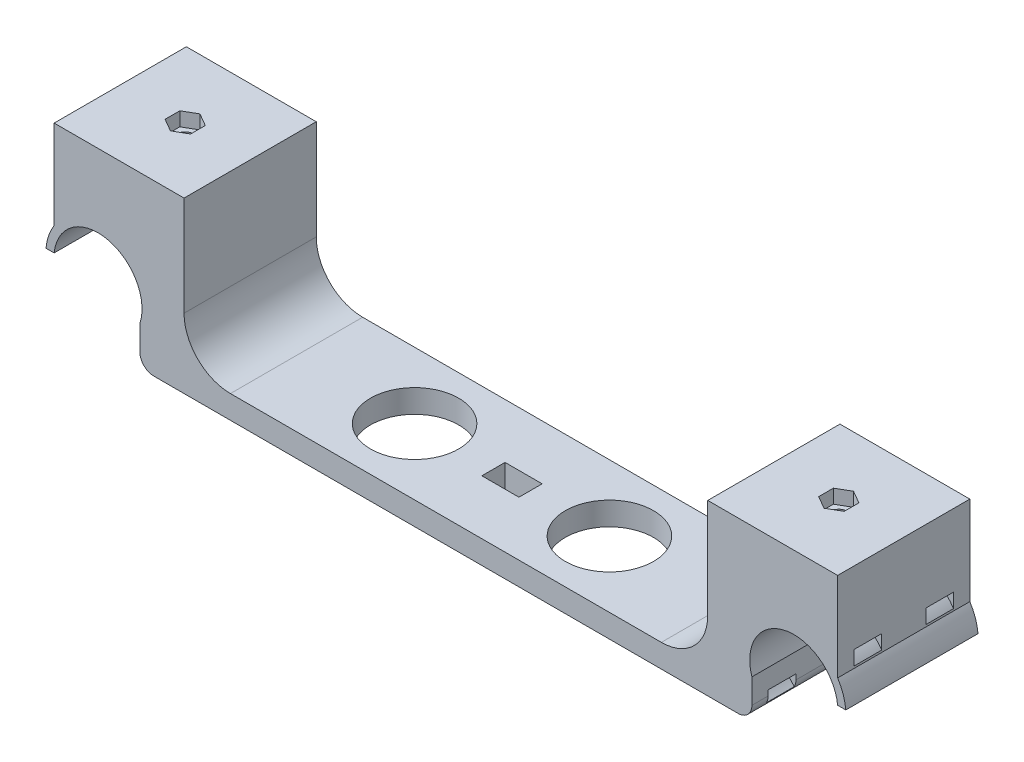
SolidWorks part; units mm, degrees
ref_plane "Front Plane" through (0, 0, 0) normal (0, 0, 1) x (1, 0, 0)
ref_plane "Top Plane" through (0, 0, 0) normal (0, 1, 0) x (1, 0, 0)
ref_plane "Right Plane" through (0, 0, 0) normal (1, 0, 0) x (0, 0, -1)
sketch "Sketch7" plane through (0, 0, 0) normal (0, 0, 1) x (1, 0, 0)
  line L0 (-35.0092, -3.4353) -> (114.9908, -3.4353)
  line L1 (-16.4565, 1.5647) -> (96.438, 1.5647)
  line L8 (126.1962, 6.8147) -> (124.438, 6.8147)
  line L9 (126.1962, 8.8147) -> (124.438, 8.8147)
  line L10 (39.9908, -3.4353) -> (39.9908, 54.826) construction
  line L11 (-46.2147, 8.8147) -> (-44.4565, 8.8147)
  line L12 (-46.2147, 6.8147) -> (-44.4565, 6.8147)
  line L19 (-44.4565, 13.9231) -> (-44.4565, 33.0647)
  line L20 (-44.4565, 33.0647) -> (-16.4565, 33.0647)
  line L21 (-16.4565, 33.0647) -> (-16.4565, 1.5647)
  line L22 (96.438, 33.0647) -> (96.438, 1.5647)
  line L23 (124.438, 13.9231) -> (124.438, 33.0647)
  line L24 (124.438, 33.0647) -> (96.438, 33.0647)
  arc A0 (124.438, 8.8147) -> (124.438, 6.8147) centre (114.9908, 7.8147) ccw
  arc A1 (-44.4565, 6.8147) -> (-44.4565, 8.8147) centre (-35.0092, 7.8147) ccw
  arc A2 (114.9908, -3.4353) -> (126.1962, 6.8147) centre (114.9908, 7.8147) ccw
  arc A3 (-44.4565, 13.9231) -> (-46.2147, 8.8147) centre (-35.0092, 7.8147) ccw
  arc A4 (-46.2147, 6.8147) -> (-35.0092, -3.4353) centre (-35.0092, 7.8147) ccw
  arc A5 (126.1962, 8.8147) -> (124.438, 13.9231) centre (114.9908, 7.8147) ccw
  dimension "D2" = 19
  dimension "D3" = 1.75
  dimension "D11" = 28
  dimension "D5" = 2
  dimension "D1" = 150
  dimension "D4" = 5
  dimension "D6" = 1
  dimension "D12" = 31.5
extrude "Boss-Extrude3" add sketch "Sketch7" along normal blind 28.5
fillet "Fillet1" radius 10 2 edges at (96.438, 1.5647, 14.25) (-16.4565, 1.5647, 14.25)
sketch "Sketch8" plane through (0, 1.5647, 0) normal (0, 1, 0) x (1, 0, 0)
  line L0 (39.9908, 0) -> (39.9908, -28.5) construction
  line L1 (86.438, 0) -> (-6.4565, 0) construction
  line L2 (86.438, -28.5) -> (-6.4565, -28.5) construction
  line L3 (86.438, -14.25) -> (-6.4565, -14.25) construction
  line L4 (35.9908, -11.75) -> (43.9908, -11.75)
  line L5 (35.9908, -11.75) -> (35.9908, -16.75)
  line L6 (35.9908, -16.75) -> (43.9908, -16.75)
  line L7 (43.9908, -11.75) -> (43.9908, -16.75)
  line L8 (86.438, -28.5) -> (86.438, 0) construction
  line L9 (-6.4565, 0) -> (-6.4565, -28.5) construction
  circle A0 centre (60.9908, -14.25) radius 9.5
  circle A1 centre (18.9908, -14.25) radius 9.5
  dimension "D5" = 19
  dimension "D7" = 21
  dimension "D1" = 5
  dimension "D2" = 8
  dimension "D3" = 4
  dimension "D4" = 2.5
  dimension "D6" = 21
extrude "Cut-Extrude4" cut sketch "Sketch8" against normal up to surface (5 mm away) up to face at (39.9908, -3.4353, 14.25)
sketch "Sketch10" plane through (0, 33.0647, 0) normal (0, 1, 0) x (1, 0, 0)
  line L0 (124.438, -14.25) -> (-44.4565, -14.25) construction
  line L1 (124.438, -28.5) -> (124.438, 0) construction
  line L2 (-44.4565, -28.5) -> (-44.4565, 0) construction
  line L10 (-16.4565, -28.5) -> (-44.4565, 0) construction
  line L11 (96.438, 0) -> (124.438, -28.5) construction
  circle A0 centre (110.438, -14.25) radius 1.75
  circle A1 centre (-30.4565, -14.25) radius 1.75
  dimension "D1" = 3.5
extrude "Cut-Extrude6" cut sketch "Sketch10" against normal blind 10
sketch "Sketch13" plane through (0, 33.0647, 0) normal (0, 1, 0) x (1, 0, 0)
  line L1 (107.688, -12.6623) -> (107.688, -15.8377)
  line L2 (107.688, -15.8377) -> (110.438, -17.4254)
  line L3 (110.438, -17.4254) -> (113.188, -15.8377)
  line L4 (113.188, -15.8377) -> (113.188, -12.6623)
  line L5 (113.188, -12.6623) -> (110.438, -11.0746)
  line L6 (110.438, -11.0746) -> (107.688, -12.6623)
  line L7 (-30.4565, -17.4254) -> (-27.7065, -15.8377)
  line L8 (-27.7065, -15.8377) -> (-27.7065, -12.6623)
  line L9 (-27.7065, -12.6623) -> (-30.4565, -11.0746)
  line L10 (-30.4565, -11.0746) -> (-33.2065, -12.6623)
  line L11 (-33.2065, -12.6623) -> (-33.2065, -15.8377)
  line L12 (-33.2065, -15.8377) -> (-30.4565, -17.4254)
  line L13 (126.1962, -28.5) -> (126.1962, 0) construction
  circle A0 centre (110.438, -14.25) radius 2.75 construction
  circle A1 centre (-30.4565, -14.25) radius 2.75 construction
  dimension "D1" = 5.5
extrude "Cut-Extrude9" cut sketch "Sketch13" against normal blind 3
ref_axis "Axis2" through (114.9908, 7.8147, 28.5) along (0, 0, -1)
ref_plane "Plane1" through (114.9908, 0, 0) normal (-1, 0, 0) x (0, 0, 1)
sketch "Sketch17" plane through (114.9908, 0, 0) normal (-1, 0, 0) x (0, 0, 1)
  line L1 (25, 19.3147) -> (19, 19.3147)
  line L2 (25, 19.3147) -> (25, 21.3147)
  line L3 (25, 21.3147) -> (19, 21.3147)
  line L4 (19, 19.3147) -> (19, 21.3147)
  line L5 (28.5, 17.3147) -> (0, 17.3147) construction
  line L10 (28.5, 33.0647) -> (28.5, 13.9231) construction
  line L11 (3.5, 21.3147) -> (9.5, 21.3147)
  line L12 (3.5, 21.3147) -> (3.5, 19.3147)
  line L13 (3.5, 19.3147) -> (9.5, 19.3147)
  line L14 (9.5, 21.3147) -> (9.5, 19.3147)
  line L15 (0, 33.0647) -> (0, 13.9231) construction
  dimension "D1" = 2
  dimension "D3" = 2
  dimension "D4" = 6
  dimension "D5" = 3.5
  dimension "D6" = 3.5
revolve "Cut-Revolve1" cut sketch "Sketch17" angle 360 about axis through (114.9908, 7.8147, 28.5) along (0, 0, -1)
sketch "Sketch14" [suppressed] plane through (0, 0, 28) normal (0, 0, 1) x (1, 0, 0)
  line L1 (-82.4893, 23.5071) -> (44.7899, 150.7863)
  line L2 (-82.4893, 23.5071) -> (44.7899, -103.7721)
  line L3 (44.7899, -103.7721) -> (172.0692, 23.5071)
  line L4 (44.7899, 150.7863) -> (172.0692, 23.5071)
  line L6 (124.4774, 32.3147) -> (96.4774, 32.3147) construction
  dimension "D1" = 180
  dimension "D2" = 180
  dimension "D3" = 45
sketch "Sketch11" [suppressed] plane through (0, 0, 28.5) normal (0, 0, 1) x (1, 0, 0)
  line L1 (-81.97, 62.499) -> (96.4919, 62.499)
  line L2 (-81.97, 62.499) -> (-81.97, -13.3564)
  line L3 (-81.97, -13.3564) -> (96.4919, -13.3564)
  line L4 (96.4919, 62.499) -> (96.4919, -13.3564)
extrude "Cut-Extrude7" [suppressed] cut sketch "Sketch11" against normal blind 56
sketch "Sketch15" [suppressed] plane through (96.4919, 0, 0) normal (-1, 0, 0) x (0, 0, 1)
  line L1 (14.4804, 34.5927) -> (32.6535, 34.5927)
  line L2 (14.4804, 34.5927) -> (14.4804, -6.1058)
  line L3 (14.4804, -6.1058) -> (32.6535, -6.1058)
  line L4 (32.6535, 34.5927) -> (32.6535, -6.1058)
extrude "Cut-Extrude10" [suppressed] cut sketch "Sketch15" against normal blind 39
ref_plane "Plane2" through (39.9908, 0, 0) normal (1, 0, 0) x (0, 0, -1)
mirror "Mirror1" about plane through (39.9908, 0, 0) normal (1, 0, 0) of "Cut-Revolve1"
sketch "Sketch18" plane through (0, 0, 28.5) normal (0, 0, 1) x (1, 0, 0)
  line L0 (-35.0092, 7.8147) -> (-25.9742, 4.8791)
  line L1 (-25.9742, 4.8791) -> (-25.9742, -3.4353)
  line L2 (-35.0092, -3.4353) -> (114.9908, -3.4353) construction
  line L3 (-25.9742, -3.4353) -> (-46.9742, -3.4353)
  line L4 (-46.9742, -3.4353) -> (-46.9742, 7.8147)
  line L5 (-46.9742, 7.8147) -> (-35.0092, 7.8147)
  line L6 (39.9908, -3.4353) -> (39.9908, 41.086) construction
  line L7 (39.9908, -11.825) -> (39.9908, 11.825) construction
  line L8 (126.9557, 7.8147) -> (114.9908, 7.8147)
  line L9 (126.9557, -3.4353) -> (126.9557, 7.8147)
  line L10 (105.9557, -3.4353) -> (126.9557, -3.4353)
  line L11 (105.9557, 4.8791) -> (105.9557, -3.4353)
  line L12 (114.9908, 7.8147) -> (105.9557, 4.8791)
  arc A1 (-44.4565, 6.8147) -> (-44.4565, 8.8147) centre (-35.0092, 7.8147) ccw construction
  dimension "D1" = 18
  dimension "D2" = 21
extrude "Cut-Extrude11" cut sketch "Sketch18" against normal blind 49
fillet "Fillet2" radius 3 2 edges at (-25.9742, -3.4353, 14.25) (105.9557, -3.4353, 14.25)
